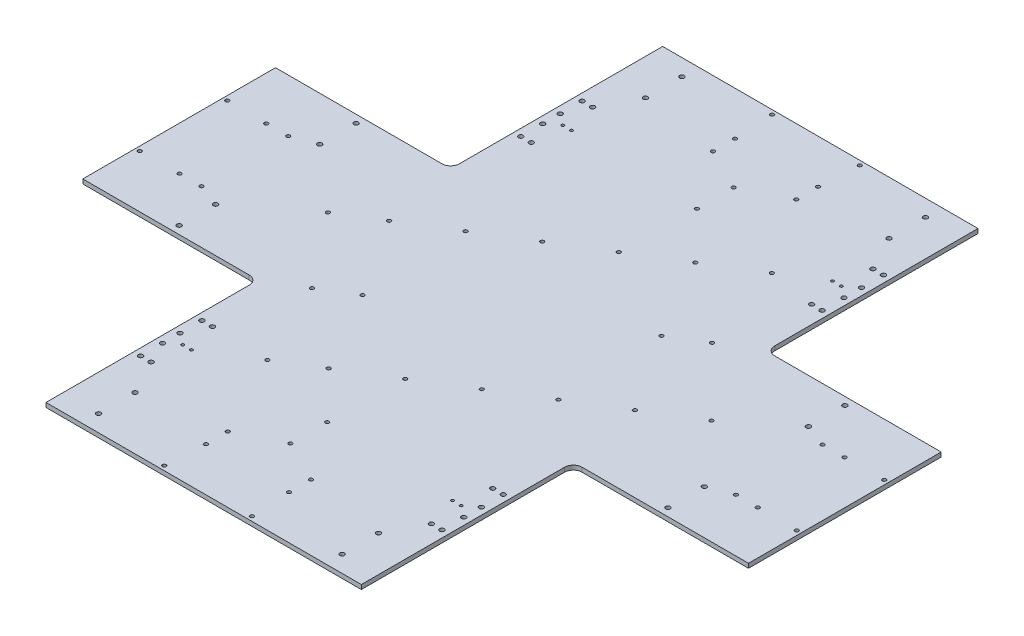
SolidWorks part; units mm, degrees
material "3.0205 (EN-AW 1200)"
ref_plane "前视基准面" through (0, 0, 0) normal (0, 0, 1) x (1, 0, 0)
ref_plane "上视基准面" through (0, 0, 0) normal (0, 1, 0) x (1, 0, 0)
ref_plane "右视基准面" through (0, 0, 0) normal (1, 0, 0) x (0, 0, -1)
other "Configuration Table"
sketch "Sketch1" plane through (0, 0, 0) normal (0, 1, 0) x (1, 0, 0)
  line L0 (180, 352) -> (-180, 352)
  line L1 (-180, 352) -> (-180, 110)
  line L2 (-180, 110) -> (-380, 110)
  line L5 (-380, 110) -> (-380, -110)
  line L6 (0, 352) -> (0, -66.8675) construction
  line L7 (-380, 0) -> (131.0517, 0) construction
  line L8 (380, 110) -> (380, -110)
  line L11 (180, 110) -> (380, 110)
  line L12 (180, 352) -> (180, 110)
  line L13 (180, -352) -> (180, -110)
  line L14 (180, -110) -> (380, -110)
  line L19 (-180, -110) -> (-380, -110)
  line L20 (-180, -352) -> (-180, -110)
  line L21 (180, -352) -> (-180, -352)
  point P21 (380, 0)
  dimension "D1" = 180
  dimension "D2" = 200
  dimension "D3" = 110
  dimension "D4" = 242
extrude "Boss-Extrude1" add sketch "Sketch1" along normal blind 5
sketch "Sketch2" plane through (0, 5, 0) normal (0, 1, 0) x (1, 0, 0)
  line L2 (380, 110) -> (180, 110) construction
  line L3 (380, -110) -> (380, 110) construction
  line L4 (-56.7455, 0) -> (47.5165, 0) construction
  line L5 (0, 54.7142) -> (0, -64.2255) construction
  line L7 (180, 352) -> (-180, 352) construction
  circle A0 centre (330, 49.5) radius 2.125
  circle A1 centre (305, 49.5) radius 2.125
  circle A7 centre (305, -49.5) radius 2.125
  circle A8 centre (330, -49.5) radius 2.125
  circle A9 centre (-330, -49.5) radius 2.125
  circle A10 centre (-305, -49.5) radius 2.125
  circle A13 centre (-305, 49.5) radius 2.125
  circle A14 centre (-330, 49.5) radius 2.125
  circle A15 centre (47.5, 302) radius 2.125
  circle A16 centre (47.5, 277) radius 2.125
  circle A17 centre (-47.5, 277) radius 2.125
  circle A18 centre (-47.5, 302) radius 2.125
  circle A19 centre (-47.5, -302) radius 2.125
  circle A20 centre (-47.5, -277) radius 2.125
  circle A21 centre (47.5, -277) radius 2.125
  circle A22 centre (47.5, -302) radius 2.125
  dimension "D1" = 60.5
  dimension "D5" = 4.25
  dimension "D7" = 4.25
  dimension "D9" = 4.25
  dimension "D10" = 4.25
  dimension "D4" = 25
  dimension "D6" = 50
  dimension "D11" = 47.5
  dimension "D12" = 50
  dimension "D13" = 25
extrude "Cut-Extrude1" cut sketch "Sketch2" against normal blind 3
sketch "Sketch4" plane through (0, 5, 0) normal (0, 1, 0) x (1, 0, 0)
  line L0 (-180, 352) -> (-180, 110) construction
  line L1 (180, 352) -> (-180, 352) construction
  line L2 (0, 46.9886) -> (0, -40.2904) construction
  line L3 (-35.103, 0) -> (92.4951, 0) construction
  line L5 (180, -352) -> (180, -110) construction
  circle A0 centre (-172, 182) radius 2.6
  circle A1 centre (-160, 182) radius 2.6
  circle A2 centre (-172, 207) radius 2.6
  circle A3 centre (-172, 227) radius 2.6
  circle A4 centre (-172, 252) radius 2.6
  circle A5 centre (-160, 252) radius 2.6
  circle A6 centre (160, 252) radius 2.6
  circle A7 centre (172, 252) radius 2.6
  circle A8 centre (172, 227) radius 2.6
  circle A9 centre (172, 207) radius 2.6
  circle A10 centre (160, 182) radius 2.6
  circle A11 centre (172, 182) radius 2.6
  circle A12 centre (172, -182) radius 2.6
  circle A13 centre (160, -182) radius 2.6
  circle A14 centre (172, -207) radius 2.6
  circle A15 centre (172, -227) radius 2.6
  circle A16 centre (172, -252) radius 2.6
  circle A17 centre (160, -252) radius 2.6
  circle A18 centre (-160, -252) radius 2.6
  circle A19 centre (-172, -252) radius 2.6
  circle A20 centre (-172, -227) radius 2.6
  circle A21 centre (-172, -207) radius 2.6
  circle A22 centre (-160, -182) radius 2.6
  circle A23 centre (-172, -182) radius 2.6
  circle A24 centre (159, -217) radius 1.6
  circle A25 centre (-159, -217) radius 1.6
  circle A26 centre (159, 217) radius 1.6
  circle A27 centre (-159, 217) radius 1.6
  circle A28 centre (149, -217) radius 1.6
  circle A29 centre (-149, -217) radius 1.6
  circle A30 centre (149, 217) radius 1.6
  circle A31 centre (-149, 217) radius 1.6
  dimension "D3" = 5.2
  dimension "D4" = 5.2
  dimension "D5" = 8
  dimension "D6" = 8
  dimension "D9" = 5.2
  dimension "D10" = 5.2
  dimension "D11" = 5.2
  dimension "D12" = 5.2
  dimension "D19" = 3.2
  dimension "D20" = 21
  dimension "D21" = 10
  dimension "D22" = 3.2
  dimension "D23" = 10
  dimension "D1" = 8
  dimension "D2" = 20
  dimension "D7" = 8
  dimension "D8" = 20
  dimension "D13" = 25
  dimension "D14" = 20
  dimension "D15" = 25
  dimension "D16" = 25
  dimension "D17" = 100
  dimension "D18" = 0
extrude "Cut-Extrude3" cut sketch "Sketch4" against normal blind 10
sketch "Sketch5" plane through (0, 5, 0) normal (0, 1, 0) x (1, 0, 0)
  line L0 (180, 352) -> (-180, 352) construction
  line L5 (-46.9195, 0) -> (66.6223, 0) construction
  line L6 (0, 59.0569) -> (0, -54.4849) construction
  line L10 (-380, 110) -> (-380, -110) construction
  line L12 (-180, 110) -> (-380, 110) construction
  line L13 (-380, -110) -> (-180, -110) construction
  circle A0 centre (-50, 347) radius 2.125
  circle A1 centre (50, 347) radius 2.125
  circle A2 centre (50, -347) radius 2.125
  circle A3 centre (-50, -347) radius 2.125
  circle A4 centre (-375, 50) radius 2.125
  circle A5 centre (-375, -50) radius 2.125
  circle A6 centre (375, -50) radius 2.125
  circle A7 centre (375, 50) radius 2.125
  dimension "D1" = 4.25
  dimension "D2" = 4.25
  dimension "D3" = 60
  dimension "D6" = 4.25
  dimension "D7" = 4.25
  dimension "5" = 5
  dimension "D4" = 50
  dimension "D5" = 50
  dimension "D8" = 60
  dimension "D9" = 5
  dimension "D10" = 5
extrude "Cut-Extrude4" cut sketch "Sketch5" against normal blind 10
fillet "Fillet1" radius 10 4 edges at (-180, 2.5, -110) (-180, 2.5, 110) (180, 2.5, 110) (180, 2.5, -110)
sketch "Sketch6" plane through (0, 5, 0) normal (0, 1, 0) x (1, 0, 0)
  line L0 (180, 352) -> (-180, 352) construction
  line L2 (180, 120) -> (180, 352) construction
  line L3 (-64.416, 0) -> (103.2752, 0) construction
  line L4 (0, 86.0771) -> (0, -73.7041) construction
  line L5 (380, 110) -> (190, 110) construction
  line L6 (380, -110) -> (380, 110) construction
  circle A0 centre (139, 333) radius 2.6
  circle A1 centre (139, 291.4) radius 2.6
  circle A2 centre (139, -291.4) radius 2.6
  circle A3 centre (139, -333) radius 2.6
  circle A4 centre (-139, -333) radius 2.6
  circle A5 centre (-139, -291.4) radius 2.6
  circle A6 centre (-139, 291.4) radius 2.6
  circle A7 centre (-139, 333) radius 2.6
  circle A8 centre (279, 101) radius 2.6
  circle A9 centre (279, 59.4) radius 2.6
  circle A10 centre (279, -59.4) radius 2.6
  circle A11 centre (279, -101) radius 2.6
  circle A12 centre (-279, -101) radius 2.6
  circle A13 centre (-279, -59.4) radius 2.6
  circle A14 centre (-279, 59.4) radius 2.6
  circle A15 centre (-279, 101) radius 2.6
  dimension "D1" = 5.2
  dimension "D2" = 5.2
  dimension "D6" = 5.2
  dimension "D7" = 5.2
  dimension "D3" = 19
  dimension "D4" = 41
  dimension "D5" = 41.6
  dimension "D8" = 9
  dimension "D9" = 41.6
  dimension "D10" = 101
extrude "Cut-Extrude5" cut sketch "Sketch6" against normal blind 10
sketch "Sketch7" plane through (0, 5, 0) normal (0, 1, 0) x (1, 0, 0)
  line L0 (197.463, 121.9013) -> (-168.3949, -103.9565) construction
  line L1 (180, 235.6925) -> (-379.973, -110) construction
  line L2 (144.6063, 226.5583) -> (333.7962, -79.9026) construction
  line L3 (-55.682, 90.1971) -> (55.682, -90.1971) construction
  line L4 (-182.9289, -112.9289) -> (182.9289, 112.9289) construction
  circle A0 centre (-55.682, 90.1971) radius 2.125
  circle A1 centre (-1.6489, 123.5538) radius 2.125
  circle A2 centre (52.3842, 156.9105) radius 2.125
  circle A3 centre (106.4174, 190.2672) radius 2.125
  circle A4 centre (-109.7152, 56.8404) radius 2.125
  circle A5 centre (-163.7483, 23.4837) radius 2.125
  circle A6 centre (-206.9749, -3.2017) radius 2.125
  circle A7 centre (-95.6108, -183.5958) radius 2.125
  circle A8 centre (-52.3842, -156.9105) radius 2.125
  circle A9 centre (1.6489, -123.5538) radius 2.125
  circle A10 centre (217.7815, 9.873) radius 2.125
  circle A11 centre (163.7483, -23.4837) radius 2.125
  circle A12 centre (109.7152, -56.8404) radius 2.125
  circle A13 centre (55.682, -90.1971) radius 2.125
  arc A14 (180, 120) -> (190, 110) centre (190, 120) ccw construction
  arc A15 (-180, -120) -> (-190, -110) centre (-190, -120) ccw construction
  point P35 (0, 0)
  point P36 (182.9289, 112.9289)
  point P37 (-182.9289, -112.9289)
  dimension "D1" = 4.25
  dimension "D2" = 4.25
  dimension "D3" = 4.25
  dimension "4.25" = 4.25
  dimension "D5" = 4.25
  dimension "D6" = 4.25
  dimension "D7" = 4.25
  dimension "D8" = 63.5
  dimension "D9" = 63.5
  dimension "D10" = 50.8
  dimension "D11" = 63.5
  dimension "D12" = 63.5
  dimension "D13" = 63.5
  dimension "D14" = 0
  dimension "D15" = 0
  dimension "D16" = 106
extrude "Cut-Extrude6" cut sketch "Sketch7" against normal blind 10
sketch "Sketch8" plane through (0, 5, 0) normal (0, 1, 0) x (1, 0, 0)
  line L0 (182.9289, 112.9289) -> (-182.9289, -112.9289) construction
  line L1 (93.4791, 124.5685) -> (153.9966, 26.5386) construction
  line L2 (-144.8767, -41.3115) -> (-92.88, -125.5389) construction
  line L3 (0, 77.1364) -> (0, -65.7088) construction
  line L4 (-60.3124, 0) -> (69.2005, 0) construction
  line L5 (180, 352) -> (-180, 352) construction
  arc A0 (180, 120) -> (190, 110) centre (190, 120) ccw construction
  arc A1 (-180, -120) -> (-190, -110) centre (-190, -120) ccw construction
  circle A2 centre (-141.2341, -87.1891) radius 2.1
  circle A3 centre (-105.4956, -65.1264) radius 2.1
  circle A4 centre (105.4956, 65.1264) radius 2.1
  circle A5 centre (141.2341, 87.1891) radius 2.1
  circle A6 centre (0, 253) radius 2.1
  circle A7 centre (0, 211) radius 2.1
  circle A8 centre (0, -211) radius 2.1
  circle A9 centre (0, -253) radius 2.1
  dimension "D3" = 4.2
  dimension "D4" = 4.2
  dimension "D5" = 4.2
  dimension "D6" = 4.2
  dimension "D8" = 21
  dimension "D11" = 4.2
  dimension "D12" = 4.2
  dimension "D1" = 70
  dimension "D2" = 70
  dimension "D7" = 21
  dimension "D9" = 21
  dimension "D10" = 21
  dimension "D13" = 99
  dimension "D14" = 42
extrude "Cut-Extrude7" cut sketch "Sketch8" against normal blind 10
